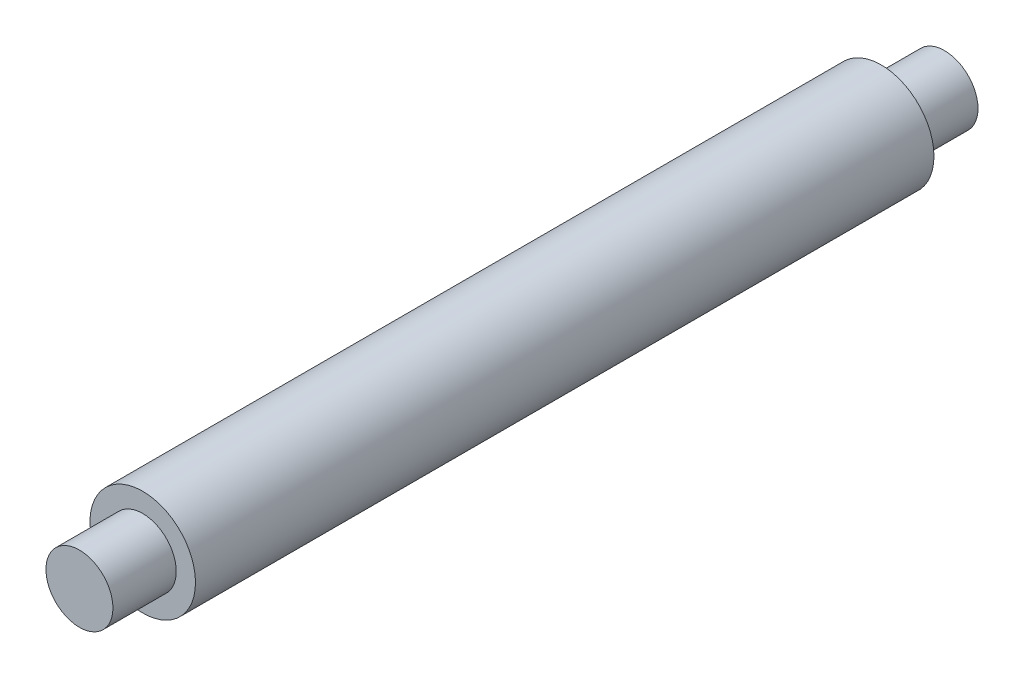
SolidWorks part; units mm, degrees
ref_plane "Front Plane" through (0, 0, 0) normal (0, 0, 1) x (1, 0, 0)
ref_plane "Top Plane" through (0, 0, 0) normal (0, 1, 0) x (1, 0, 0)
ref_plane "Right Plane" through (0, 0, 0) normal (1, 0, 0) x (0, 0, -1)
sketch "Sketch1" plane through (0, 0, 0) normal (0, 0, 1) x (1, 0, 0)
  circle A0 centre (0, 0) radius 3.175
  dimension "D1" = 6.35
extrude "Boss-Extrude1" add sketch "Sketch1" along normal mid plane 82
sketch "Sketch2" plane through (0, 0, 0) normal (0, 0, 1) x (1, 0, 0)
  circle A0 centre (0, 0) radius 5
  circle A1 centre (0, 0) radius 3.175
  circle A2 centre (0, 0) radius 3.175 construction
  dimension "D1" = 10
extrude "Boss-Extrude2" add sketch "Sketch2" along normal mid plane 70 separate body contours A0 A1 region at (-4.8586, 0, 0)
